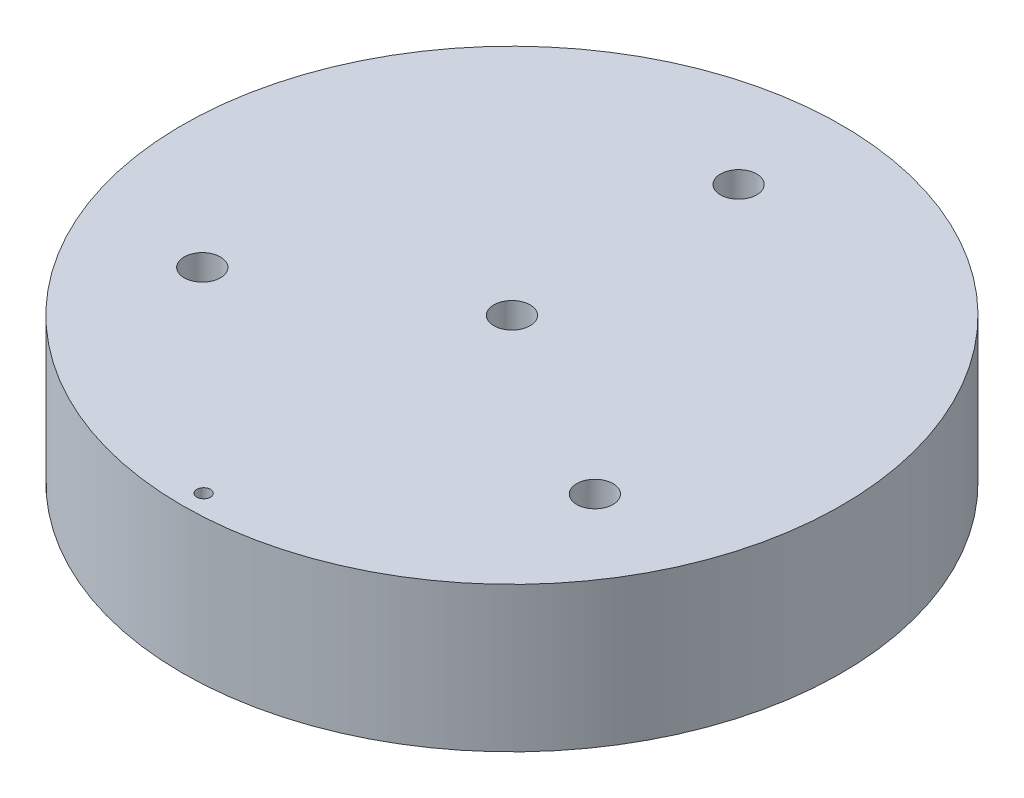
SolidWorks part; units mm, degrees
ref_plane "Ebene vorne" through (0, 0, 0) normal (0, 0, 1) x (1, 0, 0)
ref_plane "Ebene oben" through (0, 0, 0) normal (0, 1, 0) x (1, 0, 0)
ref_plane "Ebene rechts" through (0, 0, 0) normal (1, 0, 0) x (0, 0, -1)
sketch "Sketch1" plane through (0, 0, 0) normal (0, 1, 0) x (1, 0, 0)
  circle A0 centre (0, 0) radius 72.7
  dimension "D1" = 145.4
extrude "Boss-Extrude1" add sketch "Sketch1" along normal blind 32
sketch "Sketch2" plane through (0, 32, 0) normal (0, 1, 0) x (1, 0, 0)
  line L0 (0, 0) -> (0, 66.4755) construction
  circle A0 centre (0, 50) radius 4
  dimension "D1" = 8
  dimension "D2" = 50
extrude "Cut-Extrude1" cut sketch "Sketch2" against normal through all
ref_axis "Axis1" through (0, 33.6, 0) along (0, -1, 0)
pattern_circular "CirPattern1" count 3 over 360 about axis through (0, 33.6, 0) along (0, -1, 0) of "Cut-Extrude1"
sketch "Sketch3" plane through (0, 32, 0) normal (0, 1, 0) x (1, 0, 0)
  circle A0 centre (0, -68) radius 1.5
  dimension "D1" = 3
  dimension "D2" = 68
extrude "Cut-Extrude2" cut sketch "Sketch3" against normal through all
sketch "Sketch4" plane through (0, 32, 0) normal (0, 1, 0) x (1, 0, 0)
  circle A0 centre (0, 0) radius 4
  dimension "D1" = 8
extrude "Cut-Extrude3" cut sketch "Sketch4" against normal through all
